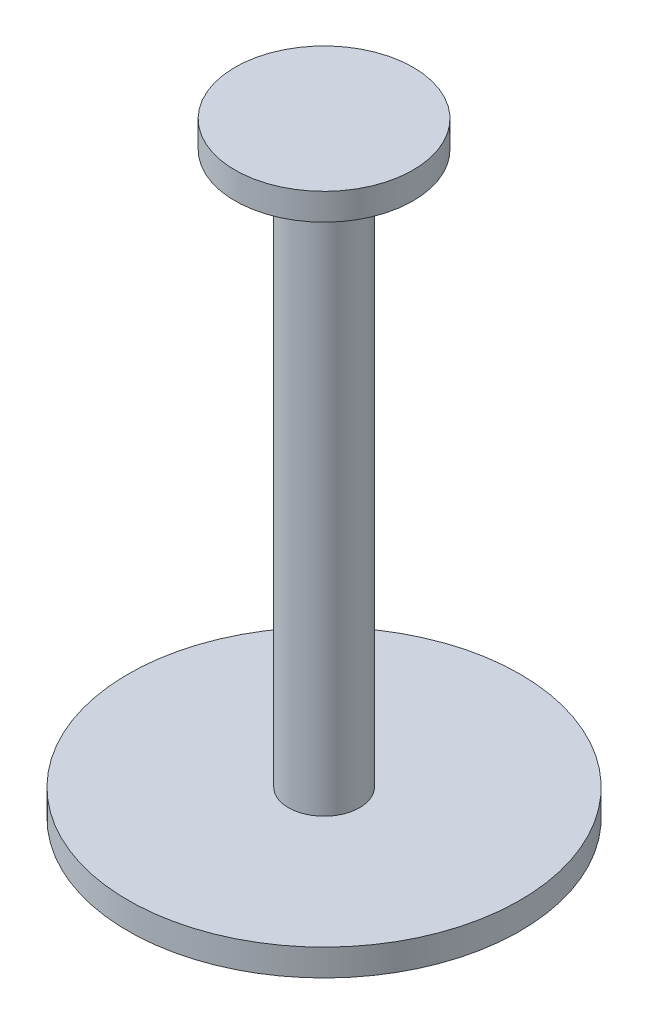
SolidWorks part; units mm, degrees
ref_plane "Front Plane" through (0, 0, 0) normal (0, 0, 1) x (1, 0, 0)
ref_plane "Top Plane" through (0, 0, 0) normal (0, 1, 0) x (1, 0, 0)
ref_plane "Right Plane" through (0, 0, 0) normal (1, 0, 0) x (0, 0, -1)
sketch "Sketch1" plane through (0, 0, 0) normal (0, 0, 1) x (1, 0, 0)
  line L0 (0, 0) -> (0, 93.5948) construction
  line L1 (0, 0) -> (4, 0)
  line L2 (4, 0) -> (4, 8)
  line L3 (4, 8) -> (22, 8)
  line L4 (22, 8) -> (22, 11)
  line L5 (22, 11) -> (4, 11)
  line L10 (0, 76) -> (0, 0)
  line L12 (4, 73) -> (4, 11)
  line L13 (4, 73) -> (10, 73)
  line L14 (10, 73) -> (10, 76)
  line L15 (10, 76) -> (0, 76)
  point P12 (4, 42)
  dimension "D1" = 4
  dimension "D2" = 22
  dimension "D3" = 10
  dimension "D4" = 4
  dimension "D5" = 62
  dimension "D6" = 3
  dimension "D7" = 3
  dimension "D8" = 8
revolve "Revolve1" add sketch "Sketch1" angle 360 about L0
thread "Thread1" pitch 1 method cut profile "Thread Profile2" start angle 0, offset 0, length 10, pitch 1, diameter 8
ref_plane "Plane2" through (4, 0, 0) normal (0, 0, 1) x (1, 0, 0)
sketch "Thread Profile2" plane through (4, 0, 0) normal (0, 0, 1) x (1, 0, 0)
  line L0 (0, 0) -> (0, 1) construction
  line L11 (0, 0) -> (0, 0.875)
  line L12 (0, 0.875) -> (-0.5413, 0.5625)
  line L13 (-0.5413, 0.5625) -> (-0.5413, 0.3125)
  line L15 (-0.5413, 0.3125) -> (0, 0)
  line L17 (-0.5413, 0.4375) -> (0, 0.4375) construction
  point P2 (0, 0)
  dimension "Pitch" = 1
  dimension "Profile_Angle" = 60
  dimension "Profile_Land" = 0.25
  dimension "Profile_Height" = 0.5413
